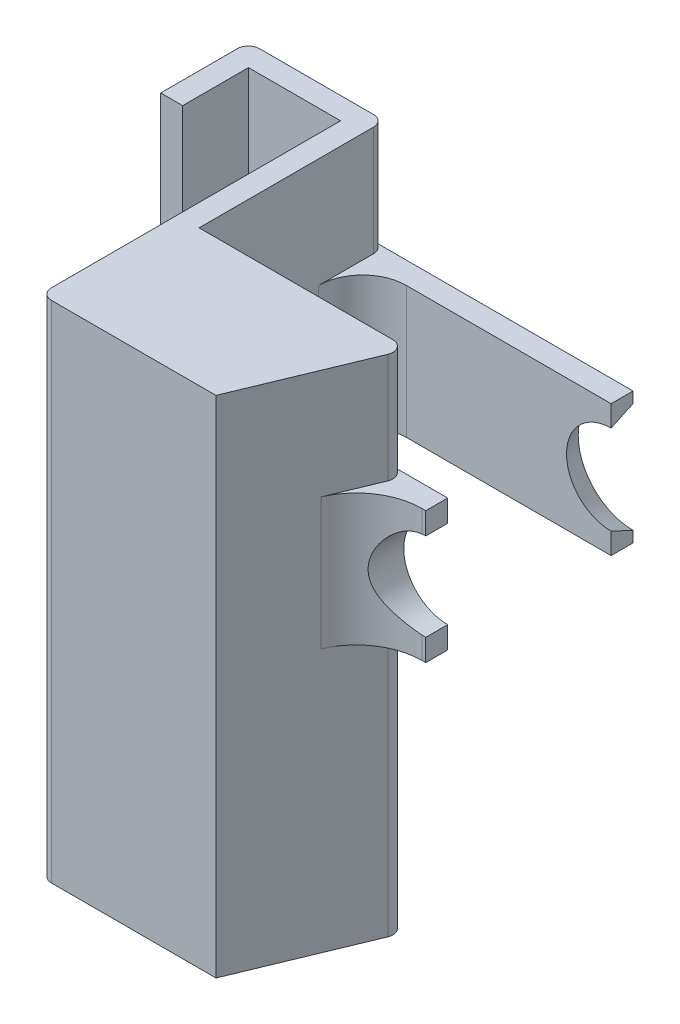
SolidWorks part; units mm, degrees
ref_plane "Front Plane" through (0, 0, 0) normal (0, 0, 1) x (1, 0, 0)
ref_plane "Top Plane" through (0, 0, 0) normal (0, 1, 0) x (1, 0, 0)
ref_plane "Right Plane" through (0, 0, 0) normal (1, 0, 0) x (0, 0, -1)
sketch "ｽｹｯﾁ1" plane through (0, 0, 0) normal (0, 1, 0) x (1, 0, 0)
  line L0 (40, -36.7) -> (52.4264, -6.7)
  line L21 (40, -36.7) -> (35.3806, -34.7866)
  line L22 (52.4264, -6.7) -> (47.807, -4.7866)
  line L23 (35.3806, -34.7866) -> (47.807, -4.7866)
  line L24 (52.4264, -6.7) -> (12.0684, -6.7) construction
  line L25 (47.807, -4.7866) -> (36.2626, -32.6571) construction
  line L26 (40, -36.7) -> (40, -14.7866) construction
  line L32 (0, -31.7) -> (5, -31.7)
  line L33 (0, -31.7) -> (0, 36.7)
  line L34 (0, 36.7) -> (5, 36.7)
  line L35 (5, -31.7) -> (5, 36.7)
  line L36 (0, 36.7) -> (-21, 36.7)
  line L37 (0, 36.7) -> (0, 31.7)
  line L38 (0, 31.7) -> (-21, 31.7)
  line L39 (-21, 36.7) -> (-21, 31.7)
  line L40 (-21, 36.7) -> (-26, 36.7)
  line L41 (-21, 36.7) -> (-21, 16.7)
  line L42 (-21, 16.7) -> (-26, 16.7)
  line L43 (-26, 36.7) -> (-26, 16.7)
  line L44 (0, -31.7) -> (40, -31.7)
  line L45 (0, -31.7) -> (0, -36.7)
  line L46 (0, -36.7) -> (40, -36.7)
  line L47 (40, -31.7) -> (40, -36.7)
  line L51 (35.1804, -36.7) -> (46.742, -36.7) construction
  point P15 (40, -6.7)
  dimension "D2" = 5
  dimension "D3" = 5
  dimension "D4" = 20
  dimension "D5" = 5
  dimension "D6" = 21
  dimension "D7" = 40
  dimension "D8" = 67.5
  dimension "D9" = 5
  dimension "D11" = 30
  dimension "D12" = 68.4
  dimension "D13" = 5
extrude "ﾎﾞｽ - 押し出し1" add sketch "ｽｹｯﾁ1" along normal blind 115 contours L23 L0 L22 | L21 L23 | L40 | L34 | L23 L21 | L40 L42 | L40 | L37 L36 L39 L38 region at (44.5672, 0, 19.2366) region at (18.349, 0, 34.2291) region at (38.1165, 0, 33.8811) region at (2.5, 0, -2.5) region at (-23.5, 0, -26.7)
fillet "ﾌｨﾚｯﾄ5" radius 2.5 1 edges at (-26, 57.5, -36.7)
fillet "ﾌｨﾚｯﾄ6" radius 2.5 1 edges at (5, 57.5, -36.7)
fillet "ﾌｨﾚｯﾄ8" radius 2.5 2 edges at (52.4264, 57.5, 6.7) (47.807, 57.5, 4.7866)
fillet "ﾌｨﾚｯﾄ10" radius 2.5 1 edges at (0, 57.5, 36.7)
fillet "ﾌｨﾚｯﾄ11" radius 2.5 1 edges at (5, 57.5, 31.7)
ref_plane "Wall Limit Plane" through (0, 115, 0) normal (0, 1, 0) x (1, 0, 0)
sketch "ｽｹｯﾁ2" plane through (0, 115, 0) normal (0, 1, 0) x (1, 0, 0)
  line L0 (70.2955, -5.553) -> (-9.1186, -5.553) construction
  line L1 (40, -36.7) -> (54.3603, -2.0311) construction
  line L2 (5, -29.2) -> (5, 34.2) construction
  line L3 (49.16, -5.553) -> (40, -5.553)
  line L4 (5, -5.553) -> (40, -5.553)
  line L5 (5, -5.553) -> (5, -36.7)
  line L6 (5, -36.7) -> (40, -36.7)
  line L8 (40, -36.7) -> (51.4697, -9.0097)
  arc A0 (51.4697, -9.0097) -> (49.16, -5.553) centre (49.16, -8.053) ccw
  point P5 (52.9015, -5.553)
  point P6 (5, -5.553)
  point P15 (52.9015, -5.553)
  dimension "D1" = 2.5
extrude "ﾎﾞｽ - 押し出し2" add sketch "ｽｹｯﾁ2" against normal blind 5
ref_plane "Rope Hanger Plane" through (0, 0, -36.7) normal (0, 0, -1) x (-1, 0, 0)
sketch "ｽｹｯﾁ3" plane through (0, 0, -36.7) normal (0, 0, -1) x (-1, 0, 0)
  line L0 (-51.66, 115) -> (-51.66, 0) construction
  line L1 (6.8518, 90) -> (-51.66, 90)
  line L2 (6.8518, 90) -> (6.8518, 60)
  line L3 (6.8518, 60) -> (-51.66, 60)
  line L5 (-61.66, 75) -> (75.3636, 75) construction
  line L6 (-49.16, 115) -> (-5, 115) construction
  line L7 (-61.66, 90) -> (-61.66, 60) construction
  line L8 (-61.66, 90) -> (-61.66, 85)
  line L9 (-61.66, 65) -> (-61.66, 60)
  line L10 (-61.66, 60) -> (-51.66, 60)
  line L11 (-61.66, 90) -> (-51.66, 90)
  arc A0 (-61.66, 65) -> (-61.66, 85) centre (-61.66, 75) ccw
  point P6 (0, 0)
  point P9 (6.8518, 75)
  point P16 (-61.66, 60)
  point P17 (-61.66, 90)
  dimension "D1" = 20
  dimension "D3" = 40
  dimension "D4" = 30
extrude "ﾎﾞｽ - 押し出し3" add sketch "ｽｹｯﾁ3" against normal blind 5 contours L10 L3 L2 L1 L11 L8 A0 L9
fillet "ﾌｨﾚｯﾄ12" radius 10 1 edges at (5, 75, -31.7)
chamfer "面取り2" distance 2.5 angle 65 1 edges at (51.66, 75, -36.7) first distance on face at (19.964, 68, -36.7)
ref_plane "Bottom Rope Hanger Plane" through (0, 0, 5.553) normal (0, 0, -1) x (-1, 0, 0)
sketch "ｽｹｯﾁ4" plane through (0, 0, 5.553) normal (0, 0, -1) x (-1, 0, 0)
  line L0 (-46.8503, 90) -> (-51.66, 90)
  line L2 (-46.8503, 60) -> (-51.66, 60)
  line L3 (-61.66, 90) -> (-61.66, 85)
  line L4 (-61.66, 65) -> (-61.66, 60)
  line L5 (-61.66, 60) -> (-51.66, 60)
  line L6 (-61.66, 90) -> (-51.66, 90)
  line L7 (-51.66, 115) -> (-51.66, 0) construction
  line L8 (-49.16, 115) -> (-5, 115) construction
  line L9 (-46.8503, 110) -> (-46.8503, 0) construction
  line L10 (-46.8503, 60) -> (-46.8503, 90)
  line L12 (-2.5, 60) -> (-61.66, 60) construction
  line L13 (-61.66, 90) -> (-2.5, 90) construction
  arc A0 (-61.66, 65) -> (-61.66, 85) centre (-61.66, 75) ccw
  point P6 (-46.8503, 60)
  point P12 (-46.8503, 90)
  dimension "D1" = 40
extrude "ﾎﾞｽ - 押し出し5" add sketch "ｽｹｯﾁ4" against normal blind 5
fillet "ﾌｨﾚｯﾄ13" radius 15 1 edges at (50.8304, 75, 10.553)
